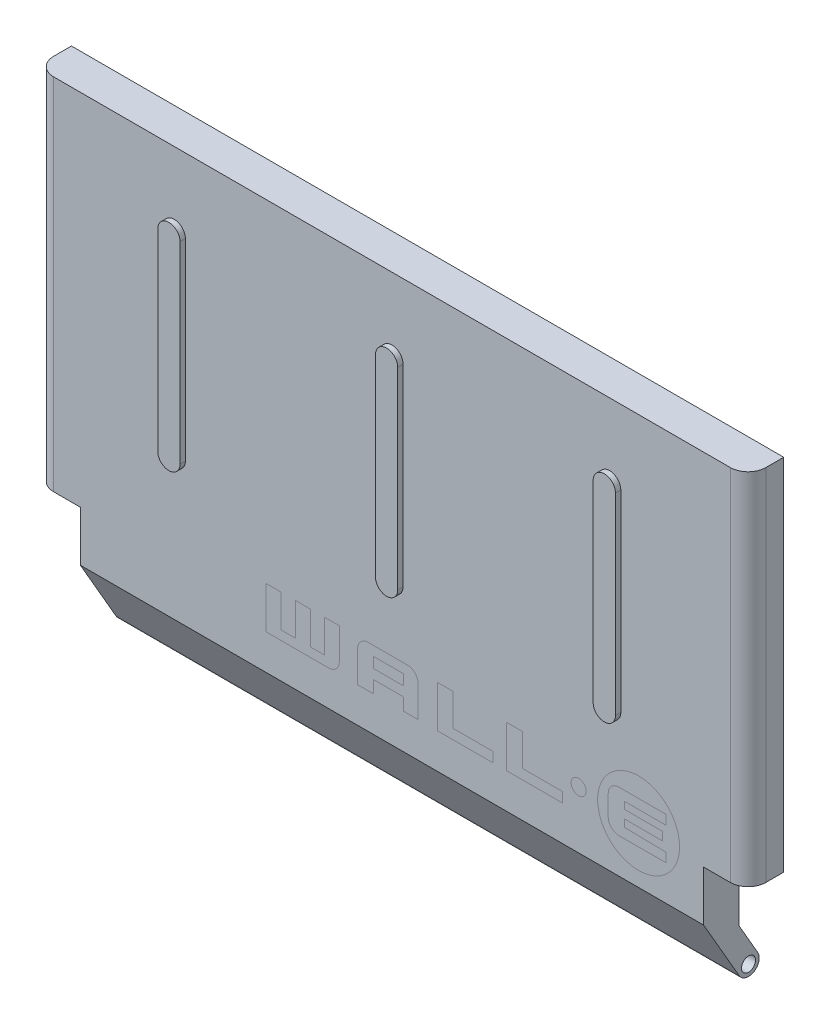
SolidWorks part; units mm, degrees
ref_plane "Front Plane" through (0, 0, 0) normal (0, 0, 1) x (1, 0, 0)
ref_plane "Top Plane" through (0, 0, 0) normal (0, 1, 0) x (1, 0, 0)
ref_plane "Right Plane" through (0, 0, 0) normal (1, 0, 0) x (0, 0, -1)
sketch "Sketch1" plane through (0, 0, 0) normal (0, 0, 1) x (1, 0, 0)
  line L0 (-49.6903, -102.7871) -> (51.9097, -102.7871)
  line L3 (-49.6903, -102.7871) -> (-49.6903, -154.0454)
  line L4 (-49.6903, -154.0454) -> (-43.3403, -154.0454)
  line L5 (-43.3403, -154.0454) -> (-43.3403, -170.0082)
  line L6 (-43.3403, -170.0082) -> (45.5597, -170.0082)
  line L7 (45.5597, -170.0082) -> (45.5597, -154.0454)
  line L9 (45.5597, -154.0454) -> (51.9097, -154.0454)
  line L10 (51.9097, -154.0454) -> (51.9097, -102.7871)
extrude "Extrude1" add sketch "Sketch1" along normal blind 5.08
fillet "Fillet1" radius 2.54 2 edges at (51.9097, -128.4163, 5.08) (-49.6903, -128.4163, 5.08)
chamfer "Chamfer1" distance 5.08 angle 60 1 edges at (1.1097, -170.0082, 5.08) first distance on face at (1.1097, -170.0082, 2.54)
sketch "Sketch3" plane through (45.5597, 0, 0) normal (1, 0, 0) x (0, 0, -1)
  line L0 (-2.6561, -165.4076) -> (0, -170.0082)
  line L1 (-5.08, -161.2093) -> (0, -170.0082) construction
  line L2 (2.6561, -168.4746) -> (0, -163.8741)
  line L3 (0, -170.0082) -> (0, -154.0454) construction
  line L4 (0, -163.8741) -> (-2.6561, -165.4076)
  arc A0 (0, -170.0082) -> (2.6561, -168.4746) centre (1.3281, -169.2414) ccw
extrude "Extrude3" add sketch "Sketch3" against normal up to surface (88.9 mm away) up to face at (-43.3403, -159.8271, 2.54)
sketch "Sketch2" plane through (45.5597, 0, 0) normal (1, 0, 0) x (0, 0, -1)
  circle A0 centre (1.3281, -169.2414) radius 1.004
extrude "Extrude2" cut sketch "Sketch2" against normal through all
sketch "Sketch4" plane through (0, 0, 5.08) normal (0, 0, 1) x (1, 0, 0)
  line L0 (1.1097, -113.3685) -> (1.1097, -140.8589) construction
  line L1 (2.6972, -113.3685) -> (2.6972, -140.8589)
  line L2 (-0.4778, -113.3685) -> (-0.4778, -140.8589)
  line L3 (49.3697, -102.7871) -> (-47.1503, -102.7871) construction
  line L4 (-29.9443, -113.3685) -> (-29.9443, -140.8589) construction
  line L5 (-31.5318, -113.3685) -> (-31.5318, -140.8589)
  line L6 (-28.3568, -113.3685) -> (-28.3568, -140.8589)
  line L7 (33.7512, -113.3685) -> (33.7512, -140.8589)
  line L8 (30.5762, -113.3685) -> (30.5762, -140.8589)
  arc A0 (2.6972, -113.3685) -> (-0.4778, -113.3685) centre (1.1097, -113.3685) ccw
  arc A1 (2.6972, -140.8589) -> (-0.4778, -140.8589) centre (1.1097, -140.8589) cw
  arc A2 (-31.5318, -113.3685) -> (-28.3568, -113.3685) centre (-29.9443, -113.3685) cw
  arc A3 (-31.5318, -140.8589) -> (-28.3568, -140.8589) centre (-29.9443, -140.8589) ccw
  arc A4 (33.7512, -113.3685) -> (30.5762, -113.3685) centre (32.1637, -113.3685) ccw
  arc A5 (33.7512, -140.8589) -> (30.5762, -140.8589) centre (32.1637, -140.8589) cw
  point P8 (1.1097, -102.7871)
  dimension "D1" = 1.5875
  dimension "D2" = 1.5875
  dimension "D3" = 1.5875
  dimension "D4" = 1.5875
extrude "Extrude4" add sketch "Sketch4" along normal blind 0.762
sketch "Sketch5" plane through (0, 0, 5.08) normal (0, 0, 1) x (1, 0, 0)
  line L0 (-16.8839, -150.2139) -> (-16.8839, -156.1947)
  line L1 (-16.8839, -156.1947) -> (-7.9276, -156.1947)
  line L2 (-6.4036, -154.6707) -> (-6.4036, -150.2139)
  line L3 (-6.4036, -150.2139) -> (-8.5448, -150.2139)
  line L4 (-8.5448, -150.2139) -> (-8.5448, -154.8945)
  line L5 (-8.5448, -154.8945) -> (-10.5319, -154.8945)
  line L6 (-10.5319, -154.8945) -> (-10.5319, -150.2139)
  line L7 (-10.5319, -150.2139) -> (-12.6419, -150.2139)
  line L8 (-12.6419, -150.2139) -> (-12.6419, -154.8945)
  line L9 (-12.6419, -154.8945) -> (-14.6905, -154.8945)
  line L10 (-14.6905, -154.8945) -> (-14.6905, -150.2139)
  line L11 (-14.6905, -150.2139) -> (-16.8839, -150.2139)
  line L12 (-3.7845, -156.1947) -> (-1.4889, -156.1947)
  line L13 (-1.4889, -156.1947) -> (-1.4889, -154.429)
  line L14 (-1.4889, -154.429) -> (2.7339, -154.429)
  line L15 (2.7339, -154.429) -> (2.7339, -156.1947)
  line L16 (2.7339, -156.1947) -> (4.8311, -156.1947)
  line L17 (4.8311, -156.1947) -> (4.8311, -151.7379)
  line L18 (3.3071, -150.2139) -> (-2.2605, -150.2139)
  line L19 (-3.7845, -151.7379) -> (-3.7845, -156.1947)
  line L20 (7.5718, -150.2139) -> (7.5718, -156.1947)
  line L21 (-1.4889, -153.0687) -> (2.7339, -153.0687)
  line L22 (-1.4889, -153.0687) -> (-1.4889, -151.5666)
  line L23 (-1.4889, -151.5666) -> (2.7339, -151.5666)
  line L24 (2.7339, -153.0687) -> (2.7339, -151.5666)
  line L25 (7.5718, -156.1947) -> (15.5296, -156.1947)
  line L26 (15.5296, -156.1947) -> (15.5296, -154.7801)
  line L27 (15.5296, -154.7801) -> (9.8494, -154.7801)
  line L28 (9.8494, -154.7801) -> (9.8494, -150.2139)
  line L29 (9.8494, -150.2139) -> (7.5718, -150.2139)
  line L30 (17.4616, -150.2139) -> (17.4616, -156.1947)
  line L31 (17.4616, -156.1947) -> (25.4194, -156.1947)
  line L32 (25.4194, -156.1947) -> (25.4194, -154.7801)
  line L33 (25.4194, -154.7801) -> (19.7392, -154.7801)
  line L34 (19.7392, -154.7801) -> (19.7392, -150.2139)
  line L35 (19.7392, -150.2139) -> (17.4616, -150.2139)
  line L36 (40.2128, -150.2139) -> (40.2128, -151.5666)
  line L37 (40.2128, -151.5666) -> (34.254, -151.5666)
  line L38 (34.254, -151.5666) -> (34.254, -152.5678)
  line L39 (34.254, -152.5678) -> (39.7162, -152.5678)
  line L40 (39.7162, -152.5678) -> (39.7162, -153.7519)
  line L41 (39.7162, -153.7519) -> (34.254, -153.7519)
  line L42 (34.254, -153.7519) -> (34.254, -154.7801)
  line L43 (34.254, -154.7801) -> (40.2128, -154.8945)
  line L44 (40.2128, -154.8945) -> (40.2128, -156.1947)
  line L45 (40.2128, -156.1947) -> (33.4832, -156.1947)
  line L46 (31.9592, -154.6707) -> (31.9592, -151.7379)
  line L47 (33.4832, -150.2139) -> (40.2128, -150.2139)
  arc A0 (-7.9276, -156.1947) -> (-6.4036, -154.6707) centre (-7.9276, -154.6707) ccw
  arc A1 (-2.2605, -150.2139) -> (-3.7845, -151.7379) centre (-2.2605, -151.7379) ccw
  arc A2 (4.8311, -151.7379) -> (3.3071, -150.2139) centre (3.3071, -151.7379) ccw
  circle A3 centre (27.7404, -153.0687) radius 1.0785
  arc A4 (31.9592, -151.7379) -> (33.4832, -150.2139) centre (33.4832, -151.7379) cw
  arc A5 (33.4832, -156.1947) -> (31.9592, -154.6707) centre (33.4832, -154.6707) cw
  circle A6 centre (36.2921, -153.2611) radius 5.8429
  dimension "D1" = 1.524
  dimension "D2" = 1.524
  dimension "D3" = 1.524
surface "Surface-Extrude1" sketch "Sketch5" parameters "D1"=1.27
split line "Split Line1"
delete or keep bodies "Body-Delete1" type delete bodies bodies 105 106 107 108 109 110 111 112
